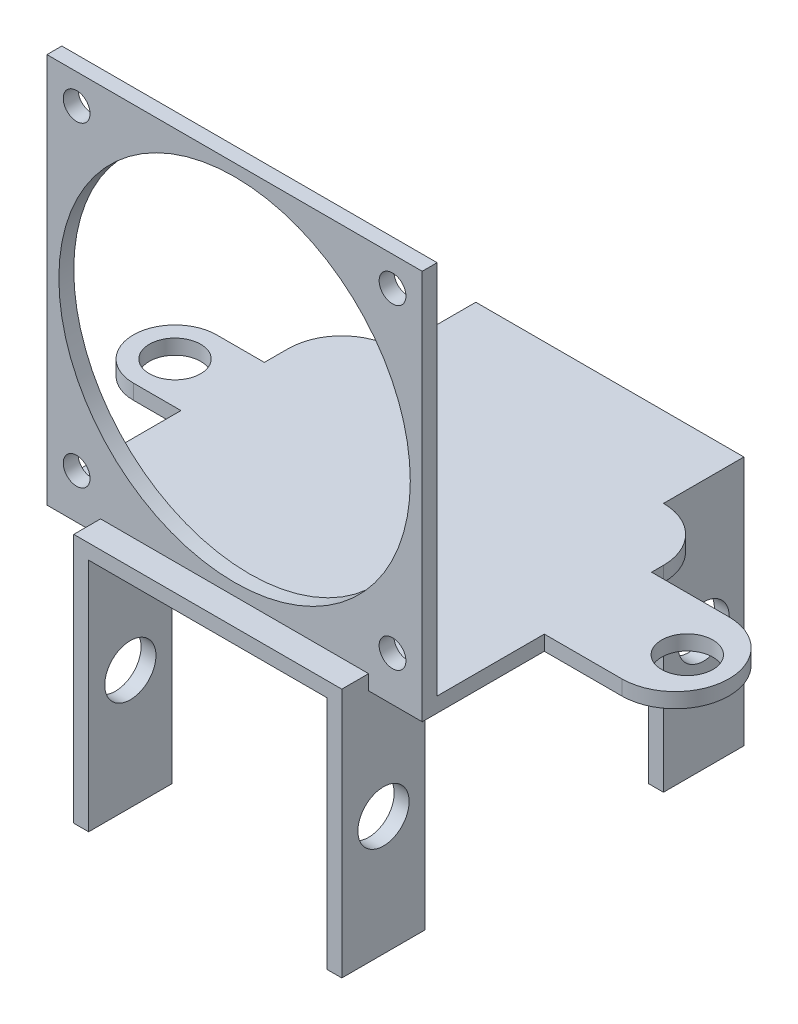
SolidWorks part; units mm, degrees
ref_plane "前视基准面" through (0, 0, 0) normal (0, 0, 1) x (1, 0, 0)
ref_plane "上视基准面" through (0, 0, 0) normal (0, 1, 0) x (1, 0, 0)
ref_plane "右视基准面" through (0, 0, 0) normal (1, 0, 0) x (0, 0, -1)
other "Configuration Table"
sketch "草图1" plane through (0, 0, 0) normal (0, 0, 1) x (1, 0, 0)
  line L0 (0, 0) -> (-29.5, 0)
  line L1 (0, 0) -> (0, 29.5)
  line L2 (0, 0) -> (-26.5165, 26.5165)
  line L3 (0, 0) -> (0, 29.5)
  line L4 (0, 31.5) -> (31.5, 31.5)
  line L5 (31.5, 31.5) -> (31.5, -34)
  line L6 (31.5, -34) -> (-31.5, -34)
  line L7 (-31.5, -34) -> (-31.5, 31.5)
  line L8 (-31.5, 31.5) -> (0, 31.5)
  circle A0 centre (0, 0) radius 29.5
  circle A1 centre (-26.5165, 26.5165) radius 2.25
  circle A2 centre (26.5165, 26.5165) radius 2.25
  circle A3 centre (26.5165, -26.5165) radius 2.25
  circle A4 centre (-26.5165, -26.5165) radius 2.25
  dimension "D1" = 59
  dimension "D4" = 31.5
  dimension "D6" = 4.5
  dimension "D2" = 45
  dimension "D3" = 37.5
  dimension "D5" = 63
  dimension "D7" = 65.5
  dimension "D8" = 31.5
extrude "凸台-拉伸1" add sketch "草图1" along normal blind 2.5 contours L5 A2 A1 A0 A3 A4 region at (15.75, 30.5912, 0)
ref_plane "基准面1" through (0, -34, 0) normal (0, 1, 0) x (1, 0, 0)
sketch "草图2" plane through (0, -34, 0) normal (0, 1, 0) x (1, 0, 0)
  line L4 (-31.5, -2.5) -> (31.5, -2.5)
  line L12 (31.5, 6.5) -> (31.5, 46.5)
  line L13 (31.5, 46.5) -> (-31.5, 46.5)
  line L14 (-31.5, -2.5) -> (-31.5, 46.5)
  line L17 (31.5, -2.5) -> (31.5, 6.5)
  line L19 (-20, -22.5) -> (20, -22.5)
  line L21 (-31.5, -2.5) -> (31.5, -2.5)
  line L24 (-20, 66.5) -> (20, 66.5)
  line L26 (0, -2.5) -> (-20, -2.5)
  line L27 (-20, -2.5) -> (-20, -22.5)
  line L28 (0, -2.5) -> (0, -6.4199)
  line L29 (0, 46.5) -> (-20, 46.5)
  line L30 (-20, 46.5) -> (-20, 66.5)
  line L31 (20, -2.5) -> (20, -22.5)
  line L32 (20, 46.5) -> (20, 66.5)
  dimension "D1" = 49
  dimension "D2" = 9
  dimension "D3" = 20
  dimension "D4" = 20
  dimension "D5" = 20
  dimension "D6" = 20
extrude "凸台-拉伸2" add sketch "草图2" along normal blind 2.5 contours L17 L12 | L24 L13 | L19 L4 region at (0, -34, -22) region at (0, -34, 12.5) region at (0, -34, -56.5)
sketch "草图3" plane through (0, -31.5, 0) normal (0, 1, 0) x (1, 0, 0)
  line L0 (20, 66.5) -> (22.5, 66.5)
  line L1 (22.5, 66.5) -> (22.5, 46.5)
  line L2 (31.5, 46.5) -> (20, 46.5) construction
  line L4 (20, 46.5) -> (20, 66.5)
  line L7 (20, 46.5) -> (20, 46)
  line L10 (0, 0) -> (0, -7.6112)
  line L11 (-20, 46.5) -> (-20, 66.5)
  line L13 (-22.5, 66.5) -> (-22.5, 46.5)
  line L14 (-20, 66.5) -> (-22.5, 66.5)
  line L15 (-22.5, -22.5) -> (-20, -22.5)
  line L16 (-22.5, -2) -> (-22.5, -22.5)
  line L18 (-20, -22.5) -> (-20, -2)
  line L19 (-22.5, -2) -> (-22.5, 0)
  line L20 (-31.5, 0) -> (31.5, 0) construction
  line L22 (-20, 0) -> (-20, -2)
  line L24 (20, 46) -> (22.5, 46)
  line L27 (-22.5, 0) -> (-22.5, 7)
  line L28 (-22.5, 7) -> (-20, 7)
  line L29 (-20, 7) -> (-20, 0)
  line L30 (20, 7) -> (20, 0)
  line L31 (22.5, 7) -> (20, 7)
  line L32 (22.5, 0) -> (22.5, 7)
  line L33 (20, 0) -> (20, -2)
  line L34 (22.5, -2) -> (22.5, 0)
  line L35 (20, -22.5) -> (20, -2)
  line L36 (22.5, -2) -> (22.5, -22.5)
  line L37 (22.5, -22.5) -> (20, -22.5)
  line L38 (22.5, 46) -> (22.5, 46.5)
  line L39 (-22.5, 46.5) -> (-22.5, 46)
  line L40 (-22.5, 46) -> (-20, 46)
  line L41 (-20, 46) -> (-20, 46.5)
  point P10 (-21.25, 7)
  line M4 (31.5, 46.5) -> (20, 46.5)
  line M7 (-20, 66.5) -> (-20, 46.5)
  line M8 (-20, 46.5) -> (-31.5, 46.5)
extrude "凸台-拉伸3" add sketch "草图3" against normal blind 42 contours L14 L13 M7 M8 | L40 L41 L39 M8 | L24 L38 L7 M4 | L1 L38 L24 L7 L4 L0 | L18 L22 L29 L28 L27 L19 L16 L15 | L36 L37 L35 L33 L30 L31 L32 L34 region at (21.25, -31.5, -46.25) region at (-21.25, -31.5, -56.5) region at (-21.25, -31.5, -46.25)
sketch "草图4" plane through (-22.5, 0, 0) normal (-1, 0, 0) x (0, 0, 1)
  line L0 (7, -31.5) -> (7, -73.5)
  line L1 (22.5, -73.5) -> (-7, -73.5) construction
  line L2 (7, -73.5) -> (22.5, -73.5)
  line L3 (22.5, -73.5) -> (22.5, -31.5)
  line L4 (22.5, -31.5) -> (7, -31.5)
  line L6 (-66.5, -31.5) -> (-46.5, -31.5) construction
  line L7 (-60.5, -31.5) -> (-60.5, -73.5)
  line L8 (-66.5, -73.5) -> (-46, -73.5) construction
  line L11 (-60.5, -31.5) -> (-66.5, -31.5)
  line L12 (-66.5, -31.5) -> (-66.5, -73.5)
  line L13 (-66.5, -73.5) -> (-60.5, -73.5)
  line L16 (-7, -73.5) -> (-7, -34) construction
  line M8 (-7, -73.5) -> (22.5, -73.5)
  line M18 (22.5, -73.5) -> (22.5, -31.5)
  line M19 (22.5, -31.5) -> (2.5, -31.5)
  dimension "D1" = 14
extrude "切除-拉伸1" cut sketch "草图4" against normal blind 60 contours L12 L13 L7 L11 | L0 M19 M8 M18 | L3 L4 L2 M18 region at (-22.5, -52.5, 14.75) region at (-22.5, -52.5, -63.5)
sketch "草图5" plane through (0, -31.5, 0) normal (0, 1, 0) x (1, 0, 0)
  line L4 (0, 0) -> (0, 11.7404)
  line L5 (-31.5, 0) -> (31.5, 0) construction
  line L7 (-31.5, 0) -> (-31.5, 46.5) construction
  line L8 (31.5, 36) -> (31.5, 18)
  line L10 (-31.5, 34) -> (-31.5, 20)
  line L11 (31.5, 46.5) -> (22.5, 46.5) construction
  line L12 (31.5, 26.5) -> (31.5, 36)
  line L13 (31.5, 36) -> (44.5, 36)
  line L14 (31.5, 26.5) -> (31.5, 18)
  line L15 (31.5, 18) -> (44.5, 18)
  line L16 (-31.5, 20) -> (-31.5, 34)
  line L17 (-31.5, 34) -> (-39.5, 34)
  line L18 (-31.5, 35.3955) -> (-31.5, 12.1429)
  line L19 (-39.5035, 20) -> (-31.5, 20)
  line L20 (31.5, 0) -> (31.5, 46.5) construction
  circle A0 centre (-39.5, 27) radius 4.3
  circle A2 centre (46.5, 27) radius 4.3
  arc A4 (44.5, 18) -> (44.5, 36) centre (44.5, 27) ccw
  arc A5 (-39.5, 34) -> (-39.5035, 20) centre (-39.5, 27) ccw
  point P0 (-46.5, 27.0018)
  point P3 (53.5, 27)
  line M19 (31.5, 0) -> (31.5, 46.5)
  dimension "D2" = 100
  dimension "D3" = 8
  dimension "D1" = 8.6
  dimension "D6" = 8.6
  dimension "D10" = 9
  dimension "D5" = 20
  dimension "D7" = 15
  dimension "D8" = 7
  dimension "D9" = 9
extrude "凸台-拉伸4" add sketch "草图5" against normal up to surface (2.5 mm away) contours L17 A5 L19 L10 A0 | L15 A4 L13 L8 A2 M19 region at (40.7026, -31.5, -27) region at (-31.7052, -31.5, -27) up to face at (0, -34, -24.75)
sketch "草图12" plane through (-22.5, 0, 0) normal (-1, 0, 0) x (0, 0, 1)
  line L0 (-46, -73.5) -> (-47, -73.5)
  line L1 (-60.5, -73.5) -> (-46, -73.5) construction
  line L2 (-47, -73.5) -> (-47, -31.5)
  line L3 (-60.5, -31.5) -> (-46.5, -31.5) construction
  line L4 (-47, -31.5) -> (-46.5, -31.5)
  line L5 (-46.5, -31.5) -> (-46, -31.5)
  line L6 (-33.5, -31.5) -> (-46.5, -31.5) construction
  line L7 (-46, -31.5) -> (-46, -73.5)
extrude "切除-拉伸9" cut sketch "草图12" against normal through all
sketch "草图13" plane through (0, -31.5, 0) normal (0, 1, 0) x (1, 0, 0)
  line L1 (-22.5, 46) -> (22.5, 46)
  line L2 (31.5, 46) -> (-22.5, 46) construction
  line L4 (22.5, 47) -> (-22.5, 47)
  line L5 (-31.5, 46.5) -> (-31.5, 47)
  line L6 (-31.5, 47) -> (-22.5, 47)
  line L7 (31.5, 46) -> (22.5, 46)
  line L8 (31.5, 46) -> (31.5, 46.5)
  line L9 (31.5, 46.5) -> (31.5, 47)
  line L10 (31.5, 47) -> (22.5, 47)
  line L11 (-22.5, 46.5) -> (-31.5, 46.5)
  line L12 (-22.5, 46.5) -> (-22.5, 46)
  line M13 (31.5, 46) -> (-22.5, 46)
  line M14 (-22.5, 46) -> (-22.5, 46.5)
  line M15 (-22.5, 46.5) -> (-31.5, 46.5)
extrude "凸台-拉伸6" add sketch "草图13" against normal up to surface (2.5 mm away) contours L9 L10 L4 L6 L5 L8 M15 M14 M13 region at (2.0769, -31.5, -46.5192) up to face at (-1.5001, -34, -18.4092)
sketch "草图14" plane through (22.5, 0, 0) normal (1, 0, 0) x (0, 0, -1)
  line L0 (0, -73.5) -> (0, -53.5)
  line L1 (-7, -73.5) -> (7, -73.5) construction
  line L2 (53.75, -73.5) -> (53.75, -53.5)
  line L3 (60.5, -73.5) -> (47, -73.5) construction
  circle A0 centre (0, -53.5) radius 4.3
  circle A1 centre (53.75, -53.5) radius 4.3
extrude "切除-拉伸10" cut sketch "草图14" against normal through all contours A0 | A1 region at (22.5, -56.4546, -2.9546) region at (22.5, -56.4546, -56.7046)
fillet "圆角3" radius 9 2 edges at (-31.5, -32.75, -47) (31.5, -32.75, -47)
